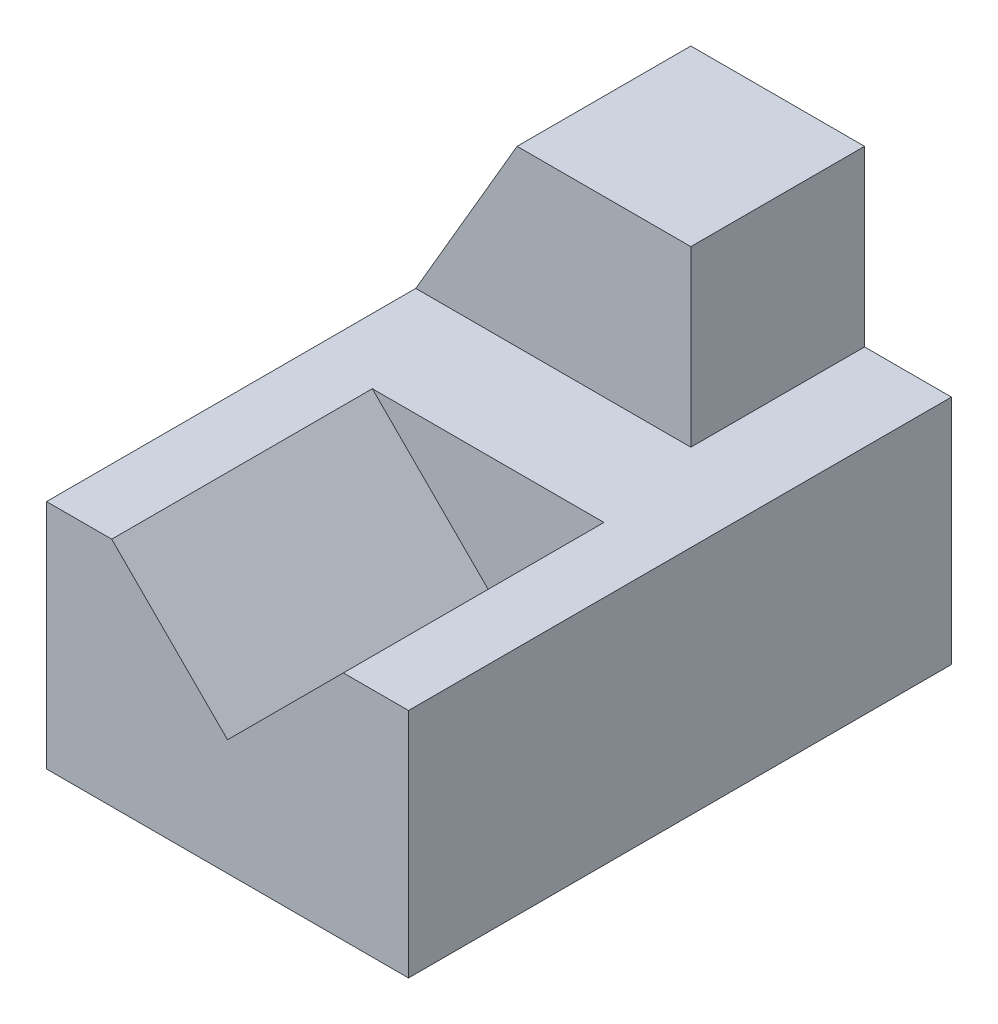
SolidWorks part; units mm, degrees
ref_plane "Front Plane" through (0, 0, 0) normal (0, 0, 1) x (1, 0, 0)
ref_plane "Top Plane" through (0, 0, 0) normal (0, 1, 0) x (1, 0, 0)
ref_plane "Right Plane" through (0, 0, 0) normal (1, 0, 0) x (0, 0, -1)
sketch "Sketch1" plane through (0, 0, 0) normal (0, 0, 1) x (1, 0, 0)
  line L0 (-41, 32) -> (-25, 16)
  line L1 (0, 0) -> (-50, 0)
  line L2 (0, 0) -> (0, 32)
  line L3 (0, 32) -> (-50, 32)
  line L4 (-50, 0) -> (-50, 32)
  line L5 (-25, 16) -> (-9, 32)
  line L6 (-12, 32) -> (-12, 56)
  line L7 (-12, 56) -> (-36, 56)
  line L8 (-36, 56) -> (-50, 32)
  point P10 (0, 0)
  point P12 (-25, 0)
  dimension "D1" = 9
  dimension "D2" = 9
  dimension "D3" = 32
  dimension "D4" = 50
  dimension "D5" = 56
  dimension "D6" = 12
  dimension "D7" = 24
  dimension "D8" = 25
  dimension "D9" = 16
extrude "Boss-Extrude1" add sketch "Sketch1" along normal blind 75 contours L5 L0 L3 L4 L1 L2 region at (-25, 13.9683, 0)
extrude "Boss-Extrude2" add sketch "Sketch1<3>" along normal blind 39 contours L0 L5 L3 region at (-25, 26.6667, 0)
sketch "Sketch1<3>" plane through (0, 0, 0) normal (0, 0, 1) x (1, 0, 0) same geometry as "Sketch1"
extrude "Boss-Extrude3" add sketch "Sketch1<4>" along normal blind 24 contours L7 L8 L3 L6 region at (-27.7634, 43.0968, 0)
sketch "Sketch1<4>" plane through (0, 0, 0) normal (0, 0, 1) x (1, 0, 0) same geometry as "Sketch1"
